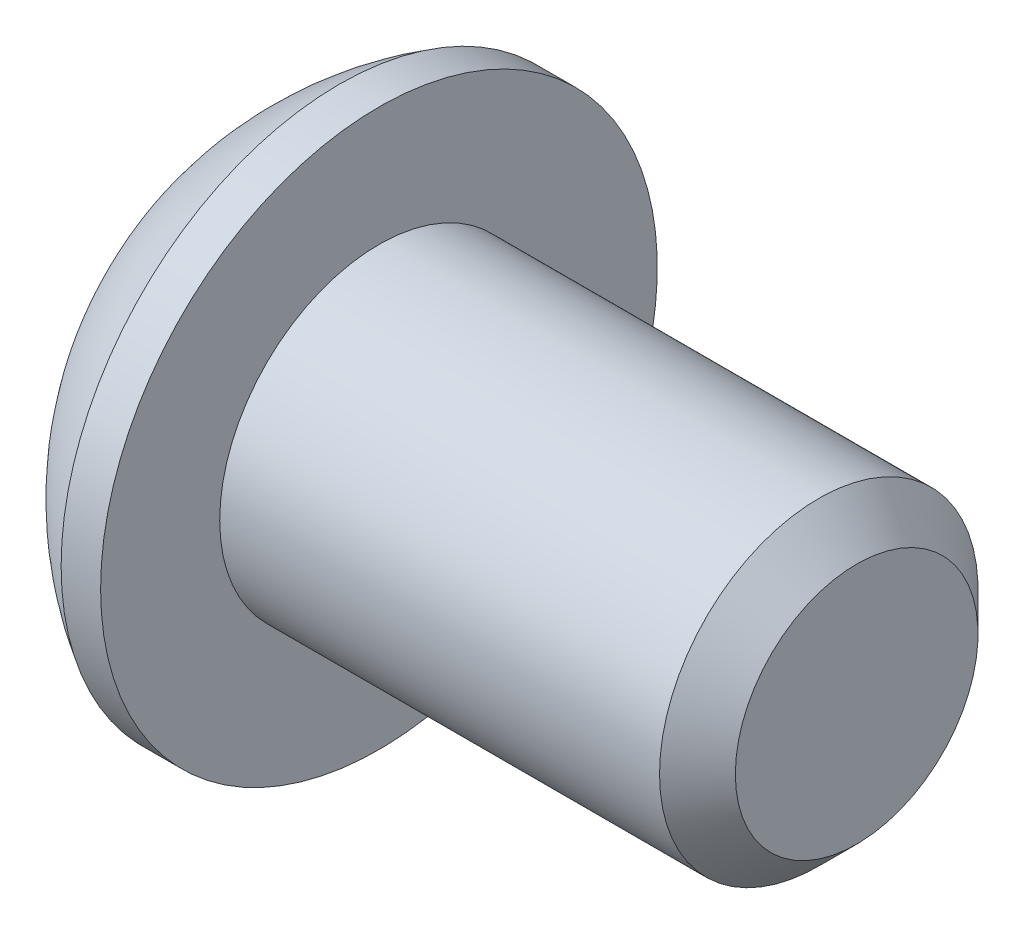
SolidWorks part; units mm, degrees
ref_plane "Plane1" through (0, 0, 0) normal (0, 0, 1) x (1, 0, 0)
ref_plane "Plane2" through (0, 0, 0) normal (0, 1, 0) x (1, 0, 0)
ref_plane "Plane3" through (0, 0, 0) normal (1, 0, 0) x (0, 0, -1)
other "Configuration Table"
sketch "BodySke" plane through (0, 0, 0) normal (0, 0, 1) x (1, 0, 0)
  line L0 (12.8778, 0) -> (12.8778, 2.4193)
  line L1 (12.1222, 3.175) -> (3.3528, 3.175)
  line L2 (3.3528, 3.175) -> (3.3528, 5.5499)
  line L3 (3.3528, 5.5499) -> (2.5654, 5.5499)
  line L4 (0, 0) -> (101.6, 0) construction
  line L5 (3.3528, -5.5499) -> (2.5654, -5.5499) construction
  line L6 (55.6768, -3.175) -> (3.3528, -3.175) construction
  line L7 (12.8778, 0) -> (0, 0)
  line L8 (0, 2.775) -> (0, -2.775) construction
  line L9 (0, 0) -> (0, 2.775)
  line L10 (12.8778, 2.4193) -> (12.1222, 3.175)
  line L11 (12.8778, -2.4193) -> (12.1222, -3.175) construction
  line L12 (4.6228, 9.525) -> (4.6228, -3.175) construction
  line L13 (3.3528, 9.525) -> (3.3528, -3.175) construction
  arc A1 (0, 2.775) -> (2.5654, 5.5499) centre (5.7851, 0) cw
  dimension "D1" = 5.5499
  dimension "Diameter" = 6.35
revolve "BaseBody" add sketch "BodySke" angle 360 about L4
cosmetic thread "ThreadCosmetic" parameters "Thread_length"=8.255, "Thread_minor"=4.8387
sketch "Sketch2" plane through (0, 0, 0) normal (0, 0, 1) x (1, 0, 0)
  line L0 (0, 1.9812) -> (2.2098, 1.9812)
  line L1 (2.2098, 1.9812) -> (3.3536, 0)
  line L3 (3.3536, 0) -> (0, 0)
  line L4 (0, 0) -> (0, 1.9812)
  line L5 (0, -1.9812) -> (2.2098, -1.9812) construction
  line L6 (0, 0) -> (47.625, 0) construction
  dimension "D2" = 60
  dimension "PreBroach_depth" = 2.2098
  dimension "PreBroach_dia" = 3.9624
revolve "PreBroach" cut sketch "Sketch2" angle 360 about L6
sketch "Sketch3" plane through (0, 0, 0) normal (1, 0, 0) x (0, 0, -1)
  line L0 (-1.9812, -1.1438) -> (-1.9812, 1.1438)
  line L1 (-1.9812, 1.1438) -> (0, 2.2877)
  line L2 (0, 2.2877) -> (1.9812, 1.1438)
  line L3 (1.9812, 1.1438) -> (1.9812, -1.1438)
  line L4 (1.9812, -1.1438) -> (0, -2.2877)
  line L5 (0, -2.2877) -> (-1.9812, -1.1438)
  dimension "Hex_size" = 3.9624
  dimension "D3" = 3.9624
  dimension "D1" = 1.9812
  dimension "D2" = 1.9812
extrude "Hex" cut sketch "Sketch3" along normal blind 2.2098
sketch "Sketch4" plane through (0, 9.525, 0) normal (1, 0, 0) x (0, 0, -1)
  line L0 (0, -9.525) -> (2.3876, -9.525)
  line L1 (0, -9.525) -> (6.1484, -5.9752) construction
  line L2 (0, -9.525) -> (1.1938, -7.4573)
  line L3 (1.9883, -8.949) -> (2.2704, -8.7861)
  line L4 (1.493, -8.0911) -> (1.7751, -7.9282)
  arc A0 (1.9883, -8.949) -> (1.493, -8.0911) centre (0, -9.525) ccw
  arc A1 (2.3876, -9.525) -> (2.2704, -8.7861) centre (0, -9.525) ccw
  arc A2 (1.1938, -7.4573) -> (1.7751, -7.9282) centre (0, -9.525) cw
  dimension "D1" = 30
  dimension "D2" = 60
  dimension "Spline_p_dim" = 0.9906
  dimension "D3" = 0.4953
extrude "Spline" [suppressed] cut sketch "Sketch4" along normal blind 2.2098
pattern_circular "CirPattern1" [suppressed] count 6 every 60 about axis through (0, 0, 0) along (1, 0, 0)
sketch "ThdSchSke" plane through (0, 0, 0) normal (0, 0, 1) x (1, 0, 0)
  line L0 (4.6228, -2.4193) -> (4.0937, -3.175)
  line L1 (4.6228, -2.4193) -> (5.1519, -3.175)
  line L2 (5.1519, -3.175) -> (5.1519, -3.9688)
  line L3 (-3.175, 0) -> (5.1513, 0) construction
  line L5 (5.1519, -3.9688) -> (4.0937, -3.9688)
  line L6 (4.0937, -3.9688) -> (4.0937, -3.175)
  dimension "Thread_minor" = 4.8387
  dimension "Diameter" = 6.35
  dimension "Start" = 4.6228
revolve "ThreadSchematic" [suppressed] cut sketch "ThdSchSke" angle 360 about L3
pattern_linear "ThdSchPat" [suppressed]
equation "\"D1@BodySke\" = \"Head_dia@BodySke\" * .5"
equation "\"Thread_minor@ThreadCosmetic\" = \"Minor_dia@BodySke\""
equation "\"D1@Sketch3\" = \"Hex_size@Sketch3\" / 2"
equation "\"D2@Sketch3\" = \"D1@Sketch3\""
equation "\"D3@Sketch3\" = \"Hex_size@Sketch3\""
equation "\"D3@Sketch4\" = \"Spline_p_dim@Sketch4\" / 2"
equation "\"D1@Sketch4\" = \"D2@Sketch4\" / 2"
equation "\"Thread_length@ThreadCosmetic\" = ((sgn( (\"Length@BodySke\" - \"Advance@BodySke\" ) - \"Thread_nom@BodySke\" )-1)*( (\"Length@BodySke\" - \"Advance@BodySke\" ) - \"Thread_nom@BodySke\" ))/-2+ \"Thread_nom@BodySke\""
equation "\"Thread_minor@ThdSchSke\" = \"Minor_dia@BodySke\""
equation "\"Diameter@ThdSchSke\" = \"Diameter@BodySke\""
equation "\"Overcut@ThdSchSke\" = \"Diameter@BodySke\" * 1.25"
equation "\"Start@ThdSchSke\" = \"Head_ht@BodySke\" + \"Length@BodySke\" - \"Thread_length@ThreadCosmetic\"  '---Non-countersunk---"
equation "\"Num_threads@ThdSchPat\" = int( \"Thread_length@ThreadCosmetic\" / \"Advance@BodySke\" + 0.999 )  + 1"
equation "\"Advance@ThdSchPat\" = \"Thread_length@ThreadCosmetic\" /  (\"Num_threads@ThdSchPat\" - 1) 'relax it"
equation "\"Num_threads@ThdSchPat\" = \"Num_threads@ThdSchPat\" - sgn( \"Num_threads@ThdSchPat\" - 1) '---chamfered tips only---"
